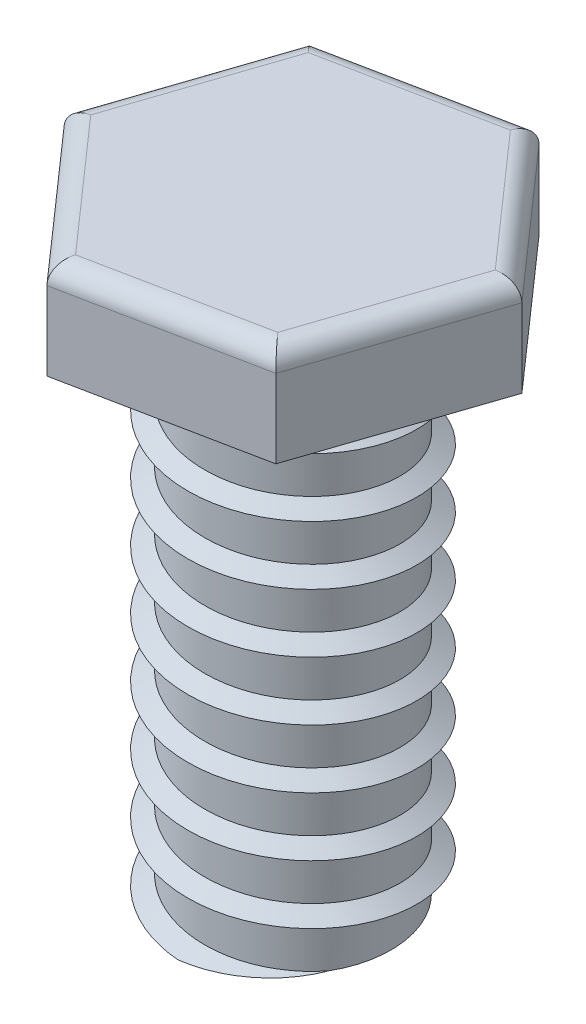
SolidWorks part; units mm, degrees
material "7075-T6 (SN)"
ref_plane "Front Plane" through (0, 0, 0) normal (0, 0, 1) x (1, 0, 0)
ref_plane "Top Plane" through (0, 0, 0) normal (0, 1, 0) x (1, 0, 0)
ref_plane "Right Plane" through (0, 0, 0) normal (1, 0, 0) x (0, 0, -1)
sketch "Sketch1" plane through (0, 0, 0) normal (0, 1, 0) x (1, 0, 0)
  circle A0 centre (0, 0) radius 5
  dimension "D1" = 10
extrude "Extrude1" add sketch "Sketch1" along normal blind 26
sketch "Sketch2" plane through (0, 26, 0) normal (0, 1, 0) x (1, 0, 0)
  line L1 (6.5621, -7.4382) -> (9.7227, 1.9639)
  line L2 (9.7227, 1.9639) -> (3.1606, 9.4021)
  line L3 (3.1606, 9.4021) -> (-6.5621, 7.4382)
  line L4 (-6.5621, 7.4382) -> (-9.7227, -1.9639)
  line L5 (-9.7227, -1.9639) -> (-3.1606, -9.4021)
  line L6 (-3.1606, -9.4021) -> (6.5621, -7.4382)
  circle A0 centre (0, 0) radius 8.5902 construction
extrude "Extrude2" add sketch "Sketch2" along normal blind 5
fillet "Fillet2" radius 1 6 edges at (-1.7008, 31, -8.4201) (-8.1424, 31, -2.7372) (-6.4417, 31, 5.683) (1.7008, 31, 8.4201) (8.1424, 31, 2.7372) (6.4417, 31, -5.683)
sketch "Sketch4" plane through (0, 26, 0) normal (0, -1, 0) x (1, 0, 0)
  circle A0 centre (0, 0) radius 5
curve "Helix/Spiral1" pitch 3 height 30 radius 5 left hand yes centre (0, 26, 0) axis (0, -1, 0) start towards (0, 0, -1)
sketch "Sketch5" plane through (0, 0, 0) normal (1, 0, 0) x (0, 0, -1)
  line L0 (5, 26) -> (5, 25)
  line L1 (5, 0) -> (5, 26) construction
  line L2 (5, 25) -> (5.866, 25.5)
  line L3 (5.866, 25.5) -> (5, 26)
  dimension "D1" = 1
  dimension "D2" = 1
  dimension "D3" = 60
sweep "Sweep1" add profiles "Sketch5" path "Helix/Spiral1"
sketch "Sketch6" plane through (0, 0, 0) normal (0, -1, 0) x (1, 0, 0)
  line L1 (-12.5591, 8.0364) -> (10.7572, 8.0364)
  line L2 (-12.5591, 8.0364) -> (-12.5591, -6.8111)
  line L3 (-12.5591, -6.8111) -> (10.7572, -6.8111)
  line L4 (10.7572, 8.0364) -> (10.7572, -6.8111)
extrude "Extrude3" cut sketch "Sketch6" along normal blind 10
fillet "Fillet3" radius 0.5 1 edges
